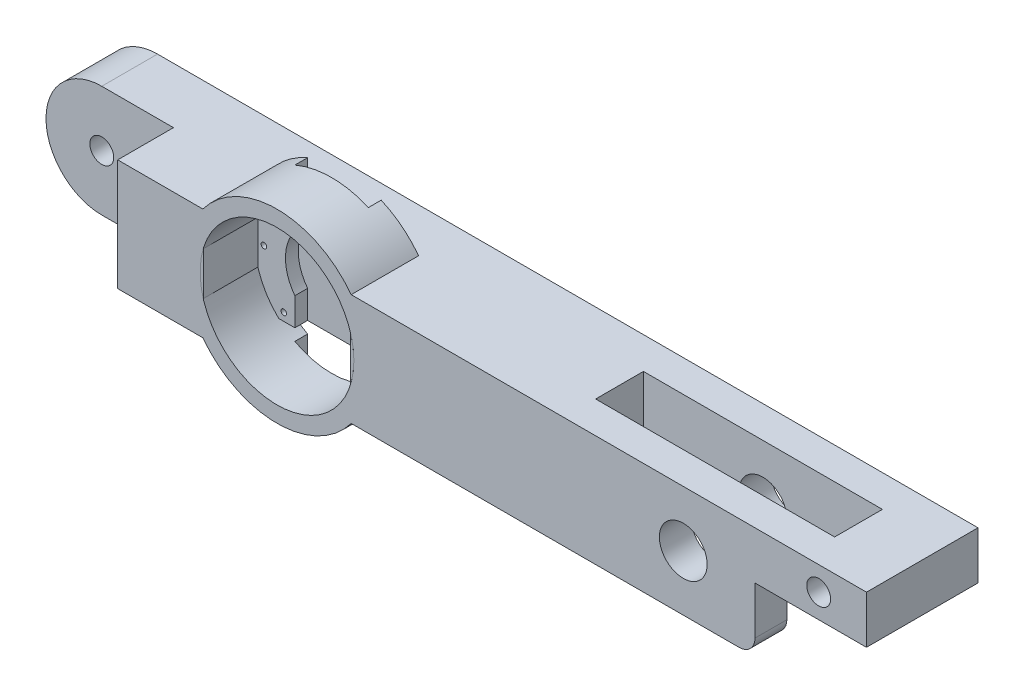
SolidWorks part; units mm, degrees
ref_plane "前视基准面" through (0, 0, 0) normal (0, 0, 1) x (1, 0, 0)
ref_plane "上视基准面" through (0, 0, 0) normal (0, 1, 0) x (1, 0, 0)
ref_plane "右视基准面" through (0, 0, 0) normal (1, 0, 0) x (0, 0, -1)
sketch "草图2" plane through (0, 0, 0) normal (0, 0, 1) x (1, 0, 0)
  line L1 (-200, 35) -> (200, 35)
  line L2 (-200, 35) -> (-200, -35)
  line L3 (-200, -35) -> (200, -35)
  line L4 (200, 35) -> (200, -35)
  line L5 (-200, 35) -> (200, -35) construction
  line L6 (-200, -35) -> (200, 35) construction
  line L7 (200, 35) -> (270, 35)
  line L8 (200, 35) -> (200, 5)
  line L9 (200, 5) -> (270, 5)
  line L10 (270, 35) -> (270, 5)
  point P0 (0, 0)
  dimension "D1" = 400
  dimension "D2" = 70
  dimension "D3" = 70
  dimension "D4" = 30
extrude "凸台-拉伸2" add sketch "草图2" along normal blind 70 contours L4 L1 L2 L3 | L10 L7 L4 L9 region at (0, 0, 0) region at (235, 20, 0)
sketch "草图3" plane through (0, 0, 70) normal (0, 0, 1) x (1, 0, 0)
  line L0 (270, 20) -> (205.533, 20) construction
  line L1 (270, 35) -> (270, 5) construction
  line L2 (240, 35) -> (240, 5) construction
  line L3 (-200, 35) -> (270, 35) construction
  line L4 (200, 5) -> (270, 5) construction
  line L5 (155, 35) -> (155, -35) construction
  line L6 (-200, -35) -> (200, -35) construction
  line L7 (-200, 0) -> (233.9858, 0) construction
  line L8 (-200, 35) -> (-200, -35) construction
  line L9 (200, 5) -> (200, -35) construction
  circle A0 centre (240, 20) radius 7.5
  circle A1 centre (155, 0) radius 15
  dimension "D2" = 15
  dimension "D4" = 30
  dimension "D1" = 30
  dimension "D3" = 45
extrude "切除-拉伸1" cut sketch "草图3" against normal through all
sketch "草图4" plane through (0, -35, 0) normal (0, -1, 0) x (1, 0, 0)
  line L0 (200, 35) -> (471.6282, 35) construction
  line L1 (200, 70) -> (200, 0) construction
  line L2 (200, 35) -> (-46.1651, 35) construction
  line L3 (170, 70) -> (140, 70) construction
  line L4 (140, 0) -> (170, 0) construction
  line L5 (170, 70) -> (140, 70)
  line L6 (140, 0) -> (170, 0)
  line L7 (170, 70) -> (170, 0) construction
  line L8 (140, 70) -> (140, 0) construction
  line L9 (155, 0) -> (155, 70) construction
  line L11 (230, 50) -> (80, 50)
  line L12 (230, 50) -> (230, 20)
  line L13 (230, 20) -> (80, 20)
  line L14 (80, 50) -> (80, 20)
  line L15 (230, 50) -> (80, 20) construction
  line L16 (230, 20) -> (80, 50) construction
  point P11 (155, 35)
  line M3 (200, 0) -> (200, 70)
  dimension "D1" = 150
  dimension "D2" = 30
extrude "切除-拉伸2" cut sketch "草图4" against normal blind 120 contours L11 L14 L13 M3 | L13 L12 L11 M3 region at (215, -35, 35) region at (140, -35, 35)
fillet "圆角1" radius 10 1 edges at (200, -35, 10)
sketch "草图5" plane through (0, 0, 70) normal (0, 0, 1) x (1, 0, 0)
  line L0 (-100, 89.4003) -> (-100, -128.0188) construction
  line L1 (-200, 35) -> (-200, -35) construction
  line L2 (-82.8995, 35) -> (-82.8995, -35) construction
  line L3 (-200, 35) -> (270, 35) construction
  line L4 (-200, -35) -> (190, -35) construction
  line L5 (-82.8995, 0) -> (-158.9987, 0) construction
  circle A0 centre (-100, 0) radius 48.25
  dimension "D2" = 96.5
  dimension "D1" = 100
extrude "切除-拉伸3" cut sketch "草图5" against normal blind 34.3
sketch "草图6" plane through (0, 0, 70) normal (0, 0, 1) x (1, 0, 0)
  line L5 (-66.7876, -35) -> (190, -35)
  line L6 (200, -25) -> (200, 5)
  line L7 (200, 5) -> (270, 5)
  line L8 (270, 5) -> (270, 35)
  line L9 (270, 35) -> (-66.7876, 35)
  line L10 (-66.7876, -35) -> (190, -35)
  line L11 (200, -25) -> (200, 5)
  line L12 (200, 5) -> (270, 5)
  line L13 (270, 5) -> (270, 35)
  line L14 (270, 35) -> (-66.7876, 35)
  circle A0 centre (-100, 0) radius 48.25
  circle A1 centre (-100, 0) radius 58.25
  arc A2 (-66.7876, -35) -> (-66.7876, 35) centre (-100, 0) ccw
  arc A3 (190, -35) -> (200, -25) centre (190, -25) ccw
  arc A4 (-66.7876, -35) -> (-66.7876, 35) centre (-100, 0) ccw
  arc A5 (190, -35) -> (200, -25) centre (190, -25) ccw
  arc M10 (-66.7876, 35) -> (-66.7876, -35) centre (-100, 0) cw
  line M11 (-66.7876, -35) -> (190, -35)
  dimension "D1" = 0
  dimension "D2" = 10
extrude "凸台-拉伸3" add sketch "草图6" against normal blind 42.3 contours L14 A1 A0 M11 | A1 L14 M11 M10 region at (-51.267, 0, 70) region at (-60.1126, -36.5671, 70)
sketch "草图7" plane through (0, 0, 70) normal (0, 0, 1) x (1, 0, 0)
  line L0 (-100, 0) -> (-146.25, 0) construction
  line L1 (-146.25, 0) -> (-53.75, 0) construction
  line L2 (-146.25, 50.9927) -> (-146.25, -50.9927)
  line L3 (-53.75, 50.9927) -> (-53.75, -50.9927)
  line L8 (270, 35) -> (-53.4375, 35)
  line L9 (-146.5625, 35) -> (-200, 35)
  line L10 (-200, 35) -> (-200, -35)
  line L11 (-200, -35) -> (-146.5625, -35)
  line L12 (-53.4375, -35) -> (190, -35)
  line L13 (200, -25) -> (200, 5)
  line L14 (200, 5) -> (270, 5)
  line L15 (270, 5) -> (270, 35)
  line L16 (270, 35) -> (-53.4375, 35)
  line L17 (-146.5625, 35) -> (-200, 35)
  line L18 (-200, 35) -> (-200, -35)
  line L19 (-200, -35) -> (-146.5625, -35)
  line L20 (-53.4375, -35) -> (190, -35)
  line L21 (200, -25) -> (200, 5)
  line L22 (200, 5) -> (270, 5)
  line L23 (270, 5) -> (270, 35)
  arc A3 (-53.4375, 35) -> (-146.5625, 35) centre (-100, 0) ccw
  arc A4 (-146.5625, -35) -> (-53.4375, -35) centre (-100, 0) ccw
  arc A5 (190, -35) -> (200, -25) centre (190, -25) ccw
  arc A6 (-53.4375, 35) -> (-146.5625, 35) centre (-100, 0) ccw
  arc A7 (-146.5625, -35) -> (-53.4375, -35) centre (-100, 0) ccw
  arc A8 (190, -35) -> (200, -25) centre (190, -25) ccw
  point P2 (-100, 0)
  circle M16 centre (-100, 0) radius 48.25
  dimension "D3" = 92.5
  dimension "D1" = 0
extrude "凸台-拉伸4" add sketch "草图7" against normal blind 42.3 separate body contours L2 M16 | L3 M16 region at (-147.0514, 0, 70) region at (-52.9486, 0, 70)
sketch "草图8" plane through (0, 0, 35.7) normal (0, 0, 1) x (1, 0, 0)
  circle A0 centre (-100, 0) radius 48.25 construction
  circle A1 centre (-100, 0) radius 48.25 construction
  circle A2 centre (-100, 0) radius 42.5 construction
  circle A3 centre (-142.5, 0) radius 1.75
  circle A4 centre (-130.052, 30.052) radius 1.75
  circle A5 centre (-100, 42.5) radius 1.75
  circle A6 centre (-69.948, 30.052) radius 1.75
  circle A7 centre (-57.5, 0) radius 1.75
  circle A8 centre (-69.948, -30.052) radius 1.75
  circle A9 centre (-100, -42.5) radius 1.75
  circle A10 centre (-130.052, -30.052) radius 1.75
  point P22 (-100, 0)
  dimension "D1" = 85
  dimension "D2" = 3.5
  dimension "D3" = 8
extrude "切除-拉伸4" cut sketch "草图8" against normal blind 42.3
sketch "草图10" plane through (0, 35, 0) normal (0, 1, 0) x (1, 0, 0)
  line L1 (-100, -35.7) -> (-71, -35.7)
  line L2 (-100, -35.7) -> (-100, -27.7)
  line L3 (-100, -27.7) -> (-71, -27.7)
  line L4 (-71, -35.7) -> (-71, -27.7)
  line L5 (-133.2124, -27.7) -> (-71, -27.7)
  line L6 (-133.2124, -27.7) -> (-133.2124, -35.7)
  line L7 (-133.2124, -35.7) -> (-71, -35.7)
  line L8 (-71, -27.7) -> (-71, -35.7)
  line L12 (-146.5625, -27.7) -> (-133.2124, -27.7)
  line L13 (-133.2124, -27.7) -> (-133.2124, -35.7)
  line L14 (-133.2124, -35.7) -> (-66.7876, -35.7)
  line L15 (-66.7876, -35.7) -> (-66.7876, -27.7)
  line L16 (-66.7876, -27.7) -> (-53.4375, -27.7)
  line L17 (-53.4375, -27.7) -> (-53.4375, -70)
  line L18 (-53.4375, -70) -> (270, -70)
  line L19 (270, -70) -> (270, 0)
  line L20 (270, 0) -> (-200, 0)
  line L21 (-200, 0) -> (-200, -70)
  line L22 (-200, -70) -> (-146.5625, -70)
  line L23 (-146.5625, -70) -> (-146.5625, -27.7)
  line L24 (-146.5625, -27.7) -> (-133.2124, -27.7) construction
  line L25 (-133.2124, -27.7) -> (-133.2124, -35.7) construction
  line L26 (-133.2124, -35.7) -> (-66.7876, -35.7) construction
  line L27 (-66.7876, -35.7) -> (-66.7876, -27.7) construction
  line L28 (-66.7876, -27.7) -> (-53.4375, -27.7) construction
  line L29 (-53.4375, -27.7) -> (-53.4375, -70) construction
  line L30 (-53.4375, -70) -> (270, -70) construction
  line L31 (270, -70) -> (270, 0) construction
  line L32 (270, 0) -> (-200, 0) construction
  line L33 (-200, 0) -> (-200, -70) construction
  line L34 (-200, -70) -> (-146.5625, -70) construction
  line L35 (-146.5625, -70) -> (-146.5625, -27.7) construction
  point P10 (0, 0)
  dimension "D2" = 29
  dimension "D1" = 0
sketch "草图11" plane through (0, 0, 35.7) normal (0, 0, 1) x (1, 0, 0)
  circle A0 centre (-100, 0) radius 48.25 construction
  circle A1 centre (-100, 0) radius 48.25 construction
  circle A2 centre (-100, 0) radius 29
  dimension "D1" = 58
extrude "切除-拉伸6" cut sketch "草图11" against normal blind 8
sketch "草图12" plane through (0, 0, 35.7) normal (0, 0, 1) x (1, 0, 0)
  line L0 (-100, 0) -> (-100, 72.6085) construction
  line L1 (-76.9088, 35) -> (-76.9088, 17.5441)
  line L2 (-133.2124, -35) -> (-66.7876, -35)
  line L3 (-66.7876, 35) -> (-133.2124, 35)
  line L4 (-133.2124, -35) -> (-66.7876, -35)
  line L5 (-66.7876, 35) -> (-133.2124, 35)
  line L6 (-76.9088, 35) -> (-123.0912, 35)
  line L7 (-100, 35) -> (-100, 17.5441)
  line L8 (-76.9088, 17.5441) -> (-123.0912, 17.5441)
  line L9 (-123.0912, 35) -> (-123.0912, 17.5441)
  line L10 (-100, 0) -> (-100, -49.5749) construction
  line L11 (-85.9044, -35) -> (-85.9044, -15.7731)
  line L12 (-85.9044, -35) -> (-114.0956, -35)
  line L13 (-100, -35) -> (-100, -15.7731)
  line L14 (-85.9044, -15.7731) -> (-114.0956, -15.7731)
  line L15 (-114.0956, -35) -> (-114.0956, -15.7731)
  circle A0 centre (-100, 0) radius 29 construction
  circle A1 centre (-100, 0) radius 29 construction
  arc A2 (-133.2124, 35) -> (-133.2124, -35) centre (-100, 0) ccw
  arc A3 (-66.7876, -35) -> (-66.7876, 35) centre (-100, 0) ccw
  arc A4 (-133.2124, 35) -> (-133.2124, -35) centre (-100, 0) ccw
  arc A5 (-66.7876, -35) -> (-66.7876, 35) centre (-100, 0) ccw
  circle A6 centre (-100, 0) radius 29
  circle M14 centre (-100, 0) radius 29
  line M24 (-66.7876, 35) -> (-133.2124, 35)
  dimension "D1" = 0
extrude "切除-拉伸7" cut sketch "草图12" against normal blind 8 contours L6 L9 L7 M14 | L7 L1 M24 M14 | L15 L4 L13 M14 | L13 L12 L11 M14 region at (-86.2526, 29.706, 35.7) region at (-113.7474, 29.706, 35.7) region at (-92.3629, -31.3259, 35.7) region at (-107.6371, -31.3259, 35.7)
sketch "草图13" plane through (-200, 0, 0) normal (-1, 0, 0) x (0, 0, 1)
  line L0 (70, 9.5592) -> (50, 9.5592) construction
  line L1 (70, 35) -> (70, -35) construction
  line L2 (70, -35) -> (0, -35) construction
  line L7 (35, -35) -> (35, -5.5599) construction
  line L8 (0, -35) -> (35, -35)
  line L9 (35, 35) -> (35, -35)
  line L10 (0, 35) -> (35, 35)
  line L11 (0, 35) -> (0, -35)
  line L12 (70, 35) -> (0, 35) construction
  dimension "D2" = 35
  dimension "D3" = 70
  dimension "D4" = 35
extrude "凸台-拉伸5" add sketch "草图13" along normal blind 80 contours L8 L9 L10 L11
fillet "圆角2" radius 35 2 edges at (-280, 35, 17.5) (-280, -35, 17.5)
sketch "草图14" plane through (0, 0, 70) normal (0, 0, 1) x (1, 0, 0)
  line L7 (-146.5625, 35) -> (-200, 35)
  line L8 (-200, -35) -> (-146.5625, -35)
  line L9 (-53.4375, -35) -> (190, -35)
  line L10 (200, -25) -> (200, 5)
  line L11 (200, 5) -> (270, 5)
  line L12 (270, 5) -> (270, 35)
  line L13 (270, 35) -> (-53.4375, 35)
  line L14 (-146.5625, 35) -> (-200, 35)
  line L15 (-200, -35) -> (-146.5625, -35)
  line L16 (-53.4375, -35) -> (190, -35)
  line L17 (200, -25) -> (200, 5)
  line L18 (200, 5) -> (270, 5)
  line L19 (270, 5) -> (270, 35)
  line L20 (270, 35) -> (-53.4375, 35)
  line L22 (-200, 35) -> (-200, -35)
  line L23 (-200, 35) -> (-200, -35)
  circle A0 centre (-245, 0) radius 7.5
  arc A7 (-146.5625, -35) -> (-53.4375, -35) centre (-100, 0) ccw
  arc A8 (190, -35) -> (200, -25) centre (190, -25) ccw
  arc A9 (-53.4375, 35) -> (-146.5625, 35) centre (-100, 0) ccw
  arc A12 (-146.5625, -35) -> (-53.4375, -35) centre (-100, 0) ccw
  arc A13 (190, -35) -> (200, -25) centre (190, -25) ccw
  arc A14 (-53.4375, 35) -> (-146.5625, 35) centre (-100, 0) ccw
  dimension "D2" = 15
  dimension "D1" = 0
extrude "切除-拉伸8" cut sketch "草图14" against normal through all contours A0
sketch "草图15" plane through (0, 35, 0) normal (0, 1, 0) x (1, 0, 0)
  line L1 (-123.0912, -27.7) -> (-76.9088, -27.7)
  line L2 (-123.0912, -27.7) -> (-123.0912, -35.7)
  line L3 (-123.0912, -35.7) -> (-76.9088, -35.7)
  line L4 (-76.9088, -27.7) -> (-76.9088, -35.7)
  line L18 (270, 0) -> (-245, 0)
  line L19 (-245, 0) -> (-245, -35)
  line L20 (-245, -35) -> (-200, -35)
  line L21 (-200, -35) -> (-200, -70)
  line L22 (-200, -70) -> (-146.5625, -70)
  line L23 (-146.5625, -70) -> (-146.5625, -27.7)
  line L24 (-146.5625, -27.7) -> (-133.2124, -27.7)
  line L25 (-133.2124, -27.7) -> (-133.2124, -35.7)
  line L26 (-133.2124, -35.7) -> (-123.0912, -35.7)
  line L27 (-123.0912, -35.7) -> (-123.0912, -27.7)
  line L28 (-123.0912, -27.7) -> (-76.9088, -27.7)
  line L29 (-76.9088, -27.7) -> (-76.9088, -35.7)
  line L30 (-76.9088, -35.7) -> (-66.7876, -35.7)
  line L31 (-66.7876, -35.7) -> (-66.7876, -27.7)
  line L32 (-66.7876, -27.7) -> (-53.4375, -27.7)
  line L33 (-53.4375, -27.7) -> (-53.4375, -70)
  line L34 (-53.4375, -70) -> (270, -70)
  line L35 (270, -70) -> (270, 0)
  line L36 (270, 0) -> (-245, 0) construction
  line L37 (-245, 0) -> (-245, -35) construction
  line L38 (-245, -35) -> (-200, -35) construction
  line L39 (-200, -35) -> (-200, -70) construction
  line L40 (-200, -70) -> (-146.5625, -70) construction
  line L41 (-146.5625, -70) -> (-146.5625, -27.7) construction
  line L42 (-146.5625, -27.7) -> (-133.2124, -27.7) construction
  line L43 (-133.2124, -27.7) -> (-133.2124, -35.7) construction
  line L44 (-133.2124, -35.7) -> (-123.0912, -35.7) construction
  line L45 (-123.0912, -35.7) -> (-123.0912, -27.7) construction
  line L46 (-123.0912, -27.7) -> (-76.9088, -27.7) construction
  line L47 (-76.9088, -27.7) -> (-76.9088, -35.7) construction
  line L48 (-76.9088, -35.7) -> (-66.7876, -35.7) construction
  line L49 (-66.7876, -35.7) -> (-66.7876, -27.7) construction
  line L50 (-66.7876, -27.7) -> (-53.4375, -27.7) construction
  line L51 (-53.4375, -27.7) -> (-53.4375, -70) construction
  line L52 (-53.4375, -70) -> (270, -70) construction
  line L53 (270, -70) -> (270, 0) construction
  dimension "D1" = 0
extrude "切除-拉伸10" cut sketch "草图15" against normal mid plane 1000
